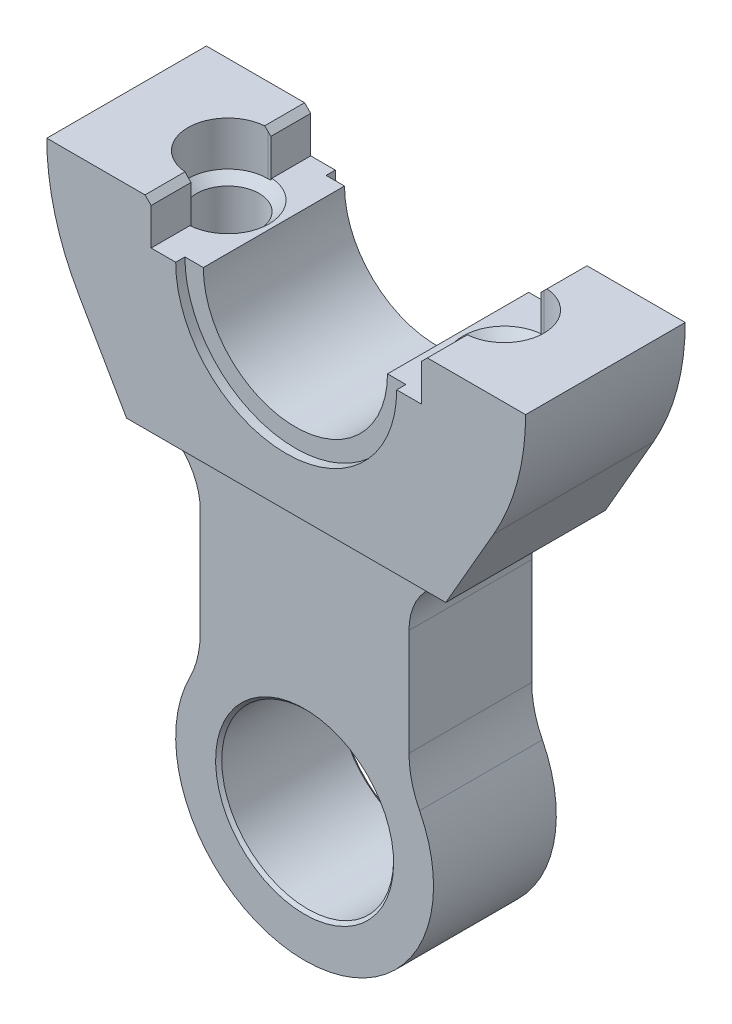
SolidWorks part; units mm, degrees
material "Простая углеродистая сталь"
ref_plane "Спереди" through (0, 0, 0) normal (0, 0, 1) x (1, 0, 0)
ref_plane "Сверху" through (0, 0, 0) normal (0, 1, 0) x (1, 0, 0)
ref_plane "Справа" through (0, 0, 0) normal (1, 0, 0) x (0, 0, -1)
sketch "Эскиз1" plane through (0, 0, 0) normal (0, 0, 1) x (1, 0, 0)
  line L0 (0, -128.6383) -> (0, 22.4317) construction
  line L1 (33.7958, -19.4639) -> (26, -33)
  line L2 (26, -33) -> (17, -33)
  line L3 (17, -33) -> (17, -60.2668)
  line L4 (-17, -33) -> (-17, -60.2668)
  line L5 (-26, -33) -> (-17, -33)
  line L6 (-33.7958, -19.4639) -> (-26, -33)
  line L7 (39, 0) -> (22, 0)
  line L8 (-75.2542, 0) -> (75.2542, 0) construction
  line L9 (22, 0) -> (22, -7)
  line L10 (-22, -7) -> (-15, -7)
  line L11 (22, -7) -> (15, -7)
  line L12 (-22, -7) -> (-22, 0)
  line L13 (-22, 0) -> (-39, 0)
  arc A0 (-39, 0) -> (-33.7958, -19.4639) centre (0, 0) ccw
  arc A1 (17, -60.2668) -> (18.7297, -67.5028) centre (33, -60.2668) ccw
  arc A2 (18.7297, -67.5028) -> (0, -98) centre (0, -77) cw
  arc A6 (33.7958, -19.4639) -> (39, 0) centre (0, 0) ccw
  arc A7 (-18.7297, -67.5028) -> (0, -98) centre (0, -77) ccw
  arc A8 (-17, -60.2668) -> (-18.7297, -67.5028) centre (-33, -60.2668) cw
  arc A9 (15, -7) -> (-15, -7) centre (0, -7) cw
  circle A10 centre (0, -77) radius 14
  point P28 (0, 0)
  dimension "D5" = 16
  dimension "D6" = 70
  dimension "D7" = 21
  dimension "D9" = 44
  dimension "D10" = 30
  dimension "D13" = 28
  dimension "D14" = 39
  dimension "D2" = 33
  dimension "D3" = 52
  dimension "D4" = 34
  dimension "D11" = 7
extrude "Бобышка-Вытянуть1" add sketch "Эскиз1" along normal mid plane 26
fillet "Скругление1" radius 10 2 edges at (-17, -33, 0) (17, -33, 0)
sketch "Эскиз2" plane through (0, 0, 0) normal (1, 0, 0) x (0, 0, -1)
  line L0 (0, 17.4918) -> (0, -107.1669) construction
  line L1 (13, 0) -> (-13, 0)
  line L3 (10, -98) -> (10, -34.6)
  line L4 (11.6, -33) -> (13, -33)
  line L5 (13, -33) -> (13, -19.4639) construction
  line L6 (13, -33) -> (13, 0)
  line L7 (-13, 0) -> (-13, -33)
  line L8 (-11.6, -33) -> (-13, -33)
  line L9 (-10, -98) -> (-10, -34.6)
  line L10 (-10, -98) -> (10, -98)
  line L11 (-13, -98) -> (13, -98) construction
  arc A0 (11.6, -33) -> (10, -34.6) centre (11.6, -34.6) ccw
  arc A1 (-11.6, -33) -> (-10, -34.6) centre (-11.6, -34.6) cw
  dimension "D1" = 1.6
  dimension "D3" = 20
extrude "Вырез-Вытянуть1" cut sketch "Эскиз2" against normal through all and the other way through all flip side to cut
sketch "Эскиз3" plane through (0, 0, 0) normal (0, 1, 0) x (1, 0, 0)
  line L0 (-43.1962, 0) -> (42.0701, 0) construction
  line L1 (0, -22.5634) -> (0, 18.8632) construction
  line L2 (22.5, 6.5) -> (22, 6.5)
  line L3 (22, -13) -> (22, 13) construction
  line L4 (22.5, -6.5) -> (22, -6.5)
  line L5 (22, 6.5) -> (22, -6.5)
  line L6 (-22, 6.5) -> (-22, -6.5)
  line L7 (-22.5, -6.5) -> (-22, -6.5)
  line L8 (-22.5, 6.5) -> (-22, 6.5)
  arc A0 (22.5, -6.5) -> (22.5, 6.5) centre (22.5, 0) ccw
  arc A1 (-22.5, -6.5) -> (-22.5, 6.5) centre (-22.5, 0) cw
  dimension "D1" = 13
  dimension "D2" = 45
extrude "Вырез-Вытянуть2" cut sketch "Эскиз3" against normal up to surface (7 mm away) up to face at (-18.5, -7, 0)
chamfer "Фаска1" distance 1 angle 45 4 edges at (22, 0, -9.75) (22, 0, 9.75) (-22, 0, 9.75) (-22, 0, -9.75)
chamfer "Фаска2" distance 0.5 angle 45 2 edges at (0, -63, -10) (0, -91, 10)
sketch "Эскиз4" plane through (0, 0, 13) normal (0, 0, 1) x (1, 0, 0)
  line L0 (0, 3.7548) -> (0, -38.5353) construction
  circle A0 centre (0, -7) radius 18
  arc A3 (-15, -7) -> (15, -7) centre (0, -7) ccw construction
  arc A4 (-15, -7) -> (15, -7) centre (0, -7) ccw construction
  dimension "D1" = 36
extrude "Вырез-Вытянуть3" cut sketch "Эскиз4" against normal blind 1.5
mirror "Зеркальное отражение1" about plane through (0, 0, 0) normal (0, 0, 1) of "Вырез-Вытянуть3"
hole_wizard "Отверстие обработанное метчиком M121" positions "Эскиз7" profile "Эскиз6" tap size "M12" standard "Iso"
sketch "Эскиз7" plane through (0, -7, 0) normal (0, 1, 0) x (1, 0, 0)
  point P0 (-22.5, 0)
  point P2 (22.5, 0)
sketch "Эскиз6" plane through (-22.5, -7, 0) normal (1, 0, 0) x (0, 0, 1)
  line L0 (0, 0) -> (0, 19.9445)
  line L1 (0, 19.9445) -> (5.1, 17)
  line L2 (5.1, 17) -> (5.1, 0)
  line L5 (5.1, 0) -> (0, 0)
  line L10 (0, 19.9445) -> (-5.1, 17) construction
  line L11 (0, -6.35) -> (0, 107.95) construction
  dimension "Диаметр сверла" = 10.2
  dimension "Глубина сверла" = 17
  dimension "Угол заточки сверла" = 120
cosmetic thread "Отверстие резьбы1" parameters "D1"=12, "D2"=12
cosmetic thread "Отверстие резьбы2" parameters "D1"=12, "D2"=12
chamfer "Фаска3" distance 1.6 angle 45 2 edges at (22.5, -7, 5.1) (-22.5, -7, 5.1)
